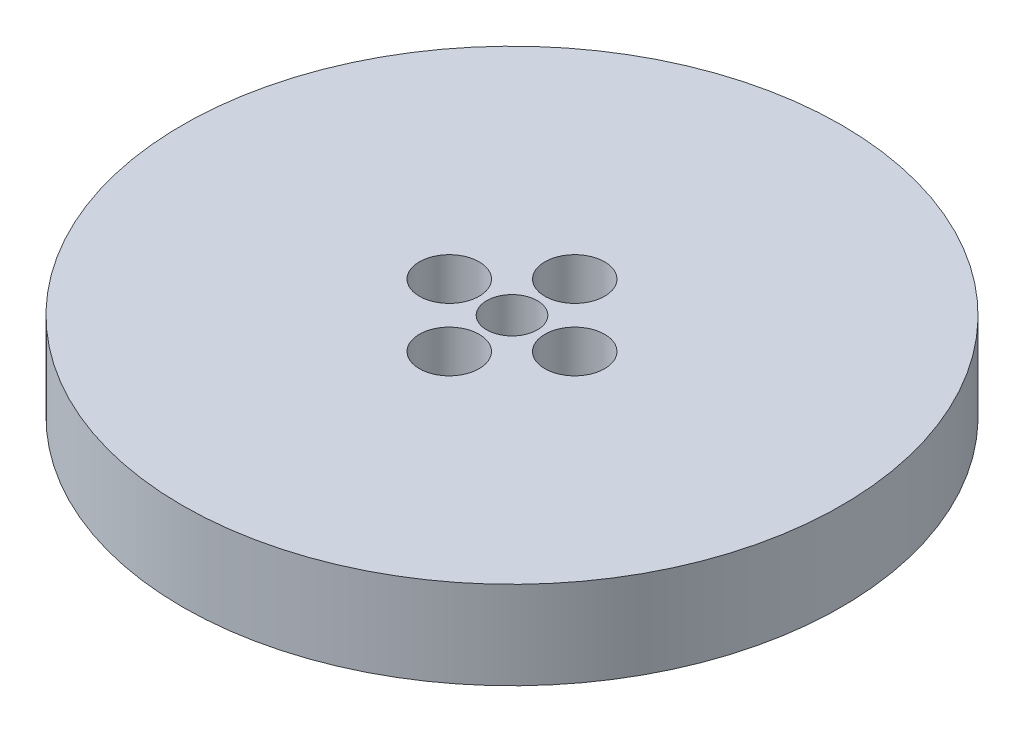
SolidWorks part; units mm, degrees
ref_plane "Front Plane" through (0, 0, 0) normal (0, 0, 1) x (1, 0, 0)
ref_plane "Top Plane" through (0, 0, 0) normal (0, 1, 0) x (1, 0, 0)
ref_plane "Right Plane" through (0, 0, 0) normal (1, 0, 0) x (0, 0, -1)
sketch "Sketch1" plane through (0, 0, 0) normal (0, 1, 0) x (1, 0, 0)
  circle A0 centre (0, 0) radius 97.5
  dimension "FLANGE_OD" = 195
extrude "Boss-Extrude1" add sketch "Sketch1" along normal blind 26
sketch "Sketch2" plane through (0, 0, 0) normal (0, 1, 0) x (1, 0, 0)
  circle A0 centre (0, 0) radius 7.5
  dimension "BORE_D" = 15
extrude "Cut-Extrude1" cut sketch "Sketch2" along normal through all
sketch "Sketch3" plane through (0, 26, 0) normal (0, 1, 0) x (1, 0, 0)
  circle A0 centre (0, 0) radius 18.5635 construction
  circle A1 centre (-18.5635, 0) radius 8.8399
  dimension "BOLT_D" = 17.6798
  dimension "BOLT_PCD" = 37.127
extrude "Cut-Extrude2" cut sketch "Sketch3" against normal blind 23.0244
pattern_circular "CirPattern1" count 4 over 360 about axis through (0, 0, 0) along (0, 1, 0) of "Cut-Extrude2"
